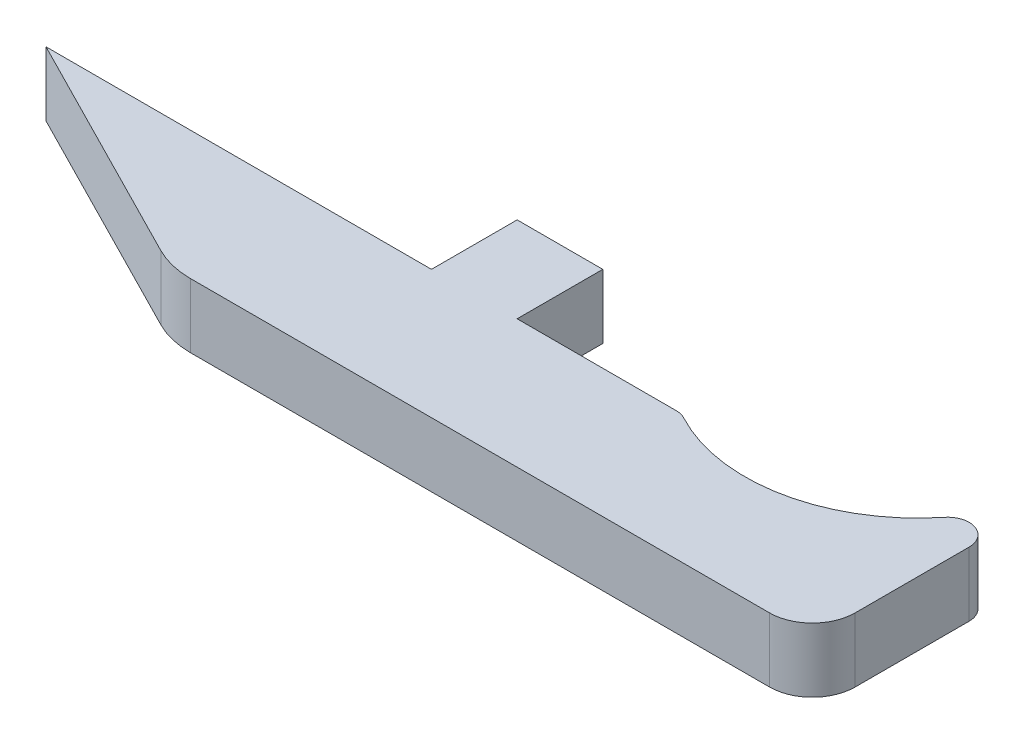
SolidWorks part; units mm, degrees
material "AISI 4130 Steel, annealed at 865C"
ref_plane "X-Y Datum" through (0, 0, 0) normal (0, 0, 1) x (1, 0, 0)
ref_plane "X-Z Datum" through (0, 0, 0) normal (0, 1, 0) x (1, 0, 0)
ref_plane "Y-Z Datum" through (0, 0, 0) normal (1, 0, 0) x (0, 0, -1)
sketch "Sketch1" plane through (0, 0, 0) normal (0, 1, 0) x (1, 0, 0)
  line L0 (59.0296, -13.5632) -> (59.0296, 11.8368) construction
  line L1 (59.0296, -11.9884) -> (3.302, -11.9884)
  line L2 (59.0296, -11.9884) -> (59.0296, -0.8632)
  line L3 (24.2316, -21.5134) -> (71.8566, -21.5134)
  line L4 (71.8566, -0.8632) -> (71.8566, -21.5134)
  line L5 (5.5225, -11.9884) -> (24.2316, -21.5134)
  line L7 (34.0975, -11.9757) -> (2.3475, -11.9757) construction
  line L8 (34.0975, -11.9757) -> (2.3475, -11.9757)
  circle A0 centre (59.0296, -0.8632) radius 12.827
  spline S0 degree 3 poles (59.0296, -13.5632) (33.6296, -13.5632) (33.6296, 11.8368) (59.0296, 11.8368) (84.4296, 11.8368) (84.4296, -13.5632) (59.0296, -13.5632) (33.6296, -13.5632) (33.6296, 11.8368) knots -0.5 0 0 0 0.5 0.5 0.5 1 1 1 1.5 1.5 1.5 weights 1 0.333333 0.333333 1 0.333333 0.333333 1 0.333333 0.333333 only from (59.0296, -13.5632) to (59.0296, -13.5632)
  spline S1 degree 3 poles (59.0296, -13.5632) (33.6296, -13.5632) (33.6296, 11.8368) (59.0296, 11.8368) (84.4296, 11.8368) (84.4296, -13.5632) (59.0296, -13.5632) (33.6296, -13.5632) (33.6296, 11.8368) knots -0.5 0 0 0 0.5 0.5 0.5 1 1 1 1.5 1.5 1.5 weights 1 0.333333 0.333333 1 0.333333 0.333333 1 0.333333 0.333333 only from (59.0296, -13.5632) to (59.0296, -13.5632) construction
  dimension "D3" = 25.654
  dimension "D5" = 9.525
  dimension "D1" = 55.7276
  dimension "D2" = 11.1252
  dimension "D4" = 3.175
  dimension "D6" = 47.625
extrude "Boss-Extrude1" add sketch "Sketch1" along normal blind 4.7625 contours L1 A0 region at (43.7069, 0, 16.3221)
fillet "Fillet1" radius 1.5875 2 edges at (52.6451, 2.3813, 11.9884) (71.8566, 2.3813, 0.8632)
fillet "Fillet2" radius 6.35 1 edges at (24.2316, 2.3813, 21.5134)
fillet "Fillet3" radius 3.175 1 edges at (71.8566, 2.3813, 21.5134)
sketch "Sketch6" plane through (0, 0, 11.9884) normal (0, 0, -1) x (-1, 0, 0)
  line L0 (-52.2351, 4.7625) -> (-5.5225, 4.7625) construction
  line L1 (-40.4475, 4.7625) -> (-34.0975, 4.7625)
  line L2 (-40.4475, 4.7625) -> (-40.4475, 0)
  line L3 (-40.4475, 0) -> (-34.0975, 0)
  line L4 (-34.0975, 4.7625) -> (-34.0975, 0)
  line L5 (-52.2351, 0) -> (-5.5225, 0) construction
  line L6 (-5.5225, 4.7625) -> (-5.5225, 0) construction
  dimension "D1" = 6.35
  dimension "D2" = 28.575
extrude "Boss-Extrude2" add sketch "Sketch6" along normal blind 6.35
